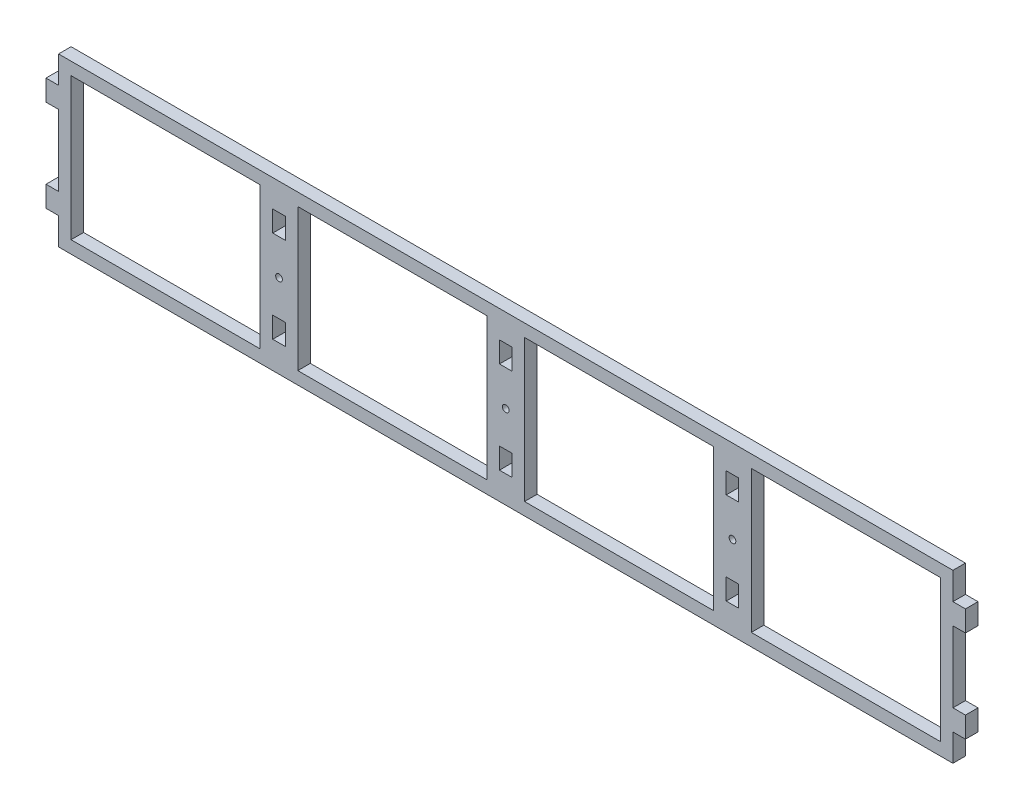
SolidWorks part; units mm, degrees
ref_plane "Front Plane" through (0, 0, 0) normal (0, 0, 1) x (1, 0, 0)
ref_plane "Top Plane" through (0, 0, 0) normal (0, 1, 0) x (1, 0, 0)
ref_plane "Right Plane" through (0, 0, 0) normal (1, 0, 0) x (0, 0, -1)
sketch "Sketch1" plane through (0, 0, 0) normal (0, 0, 1) x (1, 0, 0)
  line L1 (-214, -40) -> (214, -40)
  line L2 (-214, -40) -> (-214, 40)
  line L3 (-214, 40) -> (214, 40)
  line L4 (214, -40) -> (214, 40)
  line L5 (-214, -40) -> (214, 40) construction
  line L6 (-214, 40) -> (214, -40) construction
  point P0 (0, 0)
  dimension "D1" = 428
  dimension "D2" = 80
extrude "Boss-Extrude1" add sketch "Sketch1" along normal blind 6
sketch "Sketch2" plane through (0, 0, 6) normal (0, 0, 1) x (1, 0, 0)
  line L0 (-117.5, -40) -> (-117.5, -27) construction
  line L8 (214, -40) -> (214, 40)
  line L9 (214, 40) -> (-214, 40)
  line L10 (-214, 40) -> (-214, -40)
  line L11 (-214, -40) -> (214, -40)
  line L12 (214, -40) -> (214, 40)
  line L13 (214, 40) -> (-214, 40)
  line L14 (-214, 40) -> (-214, -40)
  line L15 (-214, -40) -> (214, -40)
  line L16 (-111.5, -40) -> (-111.5, -27) construction
  line L17 (-111.5, -40) -> (-111.5, -27) construction
  line L18 (-117.5, -34) -> (-117.5, 34)
  line L19 (-214, -34) -> (214, -34)
  line L20 (-208, 40) -> (-208, -40)
  line L21 (-117.5, 34) -> (-208, 34)
  dimension "D5" = 6
  dimension "D1" = 0
  dimension "D2" = 6
  dimension "D3" = 6
  dimension "D4" = 6
extrude "Cut-Extrude1" cut sketch "Sketch2" against normal up to next contours L18 L21 L20 L19 region at (-162.75, 0, 6)
pattern_linear "LPattern1" count 4 spacing 108.5 along (1, 0, 0) of "Cut-Extrude1"
sketch "Sketch3" plane through (0, 0, 0) normal (0, 0, -1) x (-1, 0, 0)
  line L8 (-111.5, -27) -> (-111.5, -17) construction
  line L9 (-111.5, -17) -> (-105.5, -17) construction
  line L10 (-105.5, -17) -> (-105.5, -27) construction
  line L11 (-105.5, -27) -> (-111.5, -27) construction
  line L12 (-111.5, 17) -> (-111.5, 27) construction
  line L13 (-111.5, 27) -> (-105.5, 27) construction
  line L14 (-105.5, 27) -> (-105.5, 17) construction
  line L15 (-105.5, 17) -> (-111.5, 17) construction
  line L24 (-111.5, -27) -> (-111.5, -17)
  line L25 (-111.5, -17) -> (-105.5, -17)
  line L26 (-105.5, -17) -> (-105.5, -27)
  line L27 (-105.5, -27) -> (-111.5, -27)
  line L28 (-111.5, 17) -> (-111.5, 27)
  line L29 (-111.5, 27) -> (-105.5, 27)
  line L30 (-105.5, 27) -> (-105.5, 17)
  line L31 (-105.5, 17) -> (-111.5, 17)
  line L40 (-3, 17) -> (-3, 27) construction
  line L41 (-3, 27) -> (3, 27) construction
  line L42 (3, 27) -> (3, 17) construction
  line L43 (3, 17) -> (-3, 17) construction
  line L44 (-3, -27) -> (-3, -17) construction
  line L45 (-3, -17) -> (3, -17) construction
  line L46 (3, -17) -> (3, -27) construction
  line L47 (3, -27) -> (-3, -27) construction
  line L48 (-3, 17) -> (-3, 27)
  line L49 (-3, 27) -> (3, 27)
  line L50 (3, 27) -> (3, 17)
  line L51 (3, 17) -> (-3, 17)
  line L52 (-3, -27) -> (-3, -17)
  line L53 (-3, -17) -> (3, -17)
  line L54 (3, -17) -> (3, -27)
  line L55 (3, -27) -> (-3, -27)
  line L56 (105.5, 17) -> (105.5, 27) construction
  line L57 (105.5, 27) -> (111.5, 27) construction
  line L58 (111.5, 27) -> (111.5, 17) construction
  line L59 (111.5, 17) -> (105.5, 17) construction
  line L60 (105.5, -27) -> (105.5, -17) construction
  line L61 (105.5, -17) -> (111.5, -17) construction
  line L62 (111.5, -17) -> (111.5, -27) construction
  line L63 (111.5, -27) -> (105.5, -27) construction
  line L64 (105.5, 17) -> (105.5, 27)
  line L65 (105.5, 27) -> (111.5, 27)
  line L66 (111.5, 27) -> (111.5, 17)
  line L67 (111.5, 17) -> (105.5, 17)
  line L68 (105.5, -27) -> (105.5, -17)
  line L69 (105.5, -17) -> (111.5, -17)
  line L70 (111.5, -17) -> (111.5, -27)
  line L71 (111.5, -27) -> (105.5, -27)
  circle A3 centre (108.5, 0) radius 1.6 construction
  circle A4 centre (0, 0) radius 1.6 construction
  circle A5 centre (-108.5, 0) radius 1.6 construction
  circle A6 centre (108.5, 0) radius 1.6
  circle A7 centre (0, 0) radius 1.6
  circle A8 centre (-108.5, 0) radius 1.6
extrude "Cut-Extrude2" cut sketch "Sketch3" against normal through all
sketch "Sketch4" plane through (0, 0, 0) normal (0, 0, -1) x (-1, 0, 0)
  line L0 (-111.5, 17) -> (-214, 17) construction
  line L1 (-214, -40) -> (-214, 40) construction
  line L2 (-108.5, 0) -> (-214, 0) construction
  line L3 (-220, 21.3321) -> (-220, 40) construction
  line L4 (-214, 17) -> (-220, 17)
  line L5 (-214, 17) -> (-214, 27)
  line L6 (-214, 27) -> (-220, 27)
  line L7 (-220, 17) -> (-220, 27)
  line L8 (-111.5, 27) -> (-111.5, 17) construction
  line L9 (-220, -17) -> (-220, -27)
  line L10 (-214, -27) -> (-220, -27)
  line L11 (-214, -17) -> (-214, -27)
  line L12 (-214, -17) -> (-220, -17)
  line L13 (0, 0) -> (0, 40) construction
  line L14 (-214, 40) -> (214, 40) construction
  line L15 (214, -17) -> (220, -17)
  line L16 (214, -17) -> (214, -27)
  line L17 (214, -27) -> (220, -27)
  line L18 (220, -17) -> (220, -27)
  line L19 (220, 17) -> (220, 27)
  line L20 (214, 27) -> (220, 27)
  line L21 (214, 17) -> (214, 27)
  line L22 (214, 17) -> (220, 17)
extrude "Boss-Extrude2" add sketch "Sketch4" against normal blind 6
